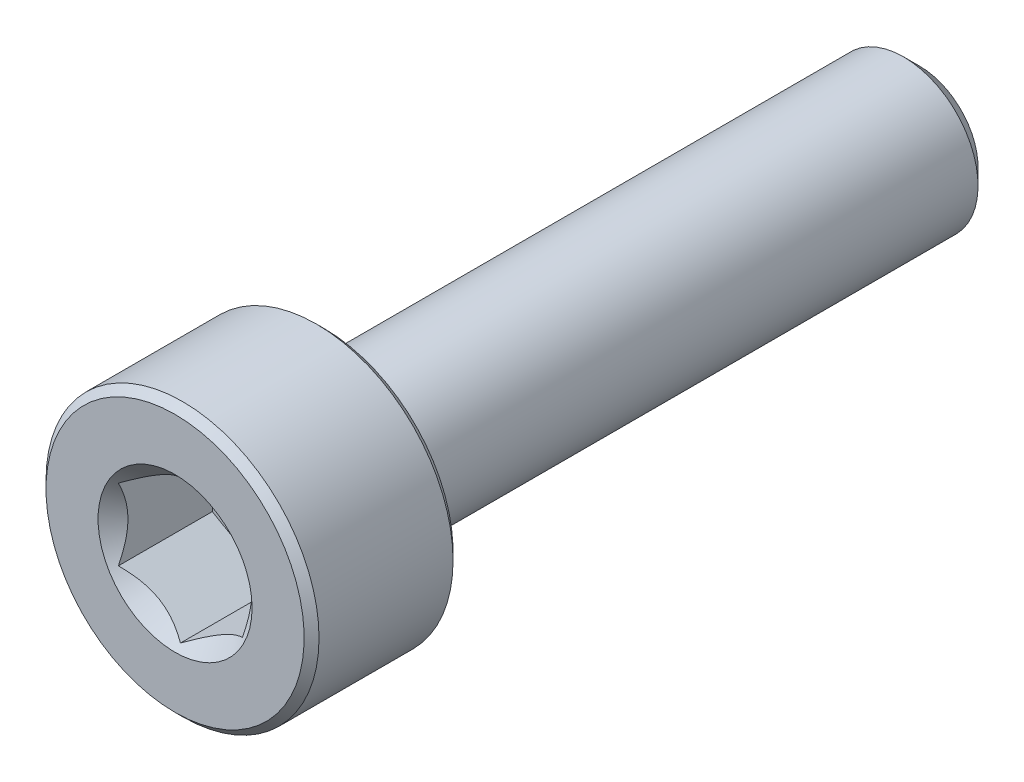
SolidWorks part; units mm, degrees
material "Alloy Steel"
ref_plane "Front Plane" through (0, 0, 0) normal (0, 0, 1) x (1, 0, 0)
ref_plane "Top Plane" through (0, 0, 0) normal (0, 1, 0) x (1, 0, 0)
ref_plane "Right Plane" through (0, 0, 0) normal (1, 0, 0) x (0, 0, -1)
sketch "Sketch1" plane through (0, 0, 0) normal (1, 0, 0) x (0, 0, -1)
  line L0 (-7.5, 0) -> (7.5, 0) construction
  line L1 (7.5, 0) -> (7.5, 1.1752) construction
  line L2 (7.5, 1.1752) -> (7.1752, 1.5) construction
  line L3 (7.1752, 1.5) -> (7.125, 1.5) construction
  line L4 (7.125, 1.5) -> (-4.5, 1.5) construction
  line L5 (-4.5, 1.5) -> (-4.5, 2.75) construction
  line L6 (-4.5, 2.75) -> (-7.5, 2.75) construction
  line L7 (-7.5, 2.75) -> (-7.5, 0) construction
  line L8 (7.5, 1.1752) -> (7.5, 1.5) construction
  line L9 (7.4687, 1.5541) -> (7.7187, 1.1211) construction
  line L10 (7.7187, 1.1211) -> (7.9687, 1.5541) construction
  line L11 (7.9687, 1.5541) -> (7.4687, 1.5541) construction
  line L12 (7.7187, 1.5541) -> (7.7188, 1.5) construction
  line L13 (7.7187, 1.1211) -> (7.7187, 1.1752) construction
  line L14 (7.6875, 1.1752) -> (7.75, 1.1752) construction
  line L15 (7.5, 1.5) -> (7.9375, 1.5) construction
  line L16 (7.4844, 1.5271) -> (7.9531, 1.5271) construction
  line L17 (7.5, 0) -> (7.5, -1.5) construction
  line L18 (-4.65, 2.75) -> (-4.5, 2.6) construction
  line L19 (-7.35, 2.75) -> (-7.5, 2.6) construction
  line L20 (-4.5, 1.5) -> (-4.5, 0) construction
  line L21 (-4.5, 0.75) -> (-0.5, 0.75) construction
  line L22 (-0.5, 0.75) -> (3.5, 0.75) construction
  line L23 (3.5, 0.75) -> (7.5, 0.75) construction
  line L24 (-0.5, 0.75) -> (-0.5, 1.5) construction
  line L25 (-0.5, 1.5) -> (-0.5, 2.75) construction
  line L26 (3.5, 0.75) -> (3.5, 2.75) construction
  point P0 (-7.5, 1.25)
  point P3 (6.25, 1.5)
  point P4 (0, 0)
  point P18 (3.5, 1.5)
  point P22 (7.7187, 1.1752)
  point P24 (7.125, 1.5)
  point P25 (7.7188, 1.5)
  point P28 (7.7187, 1.5271)
  point P29 (6.25, -1.5)
  point P30 (-0.5, 1.5)
  point P31 (-6, 2.75)
  point P37 (-5.025, 2.75)
  point P38 (-7.275, 2.75)
  point P45 (-0.5, 0.75)
  point P46 (3.5, 0.75)
  dimension "D2" = 0.0625
  dimension "D7" = 0.15
  dimension "D8" = 0.15
  dimension "D9" = 0.15
  dimension "D10" = 0.075
  dimension "D11" = 0.375
  dimension "Drive Size" = 2.5
  dimension "Head Diameter" = 5.5
  dimension "Head Height" = 3
  dimension "Thread Pitch" = 0.5
  dimension "Thread Dia" = 3
  dimension "Length" = 12
  dimension "D12" = 0.375
  dimension "D4" = 1.25
  dimension "D3" = 45
sketch "Sketch2" plane through (0, 0, 0) normal (1, 0, 0) x (0, 0, -1)
  line L0 (-7.5, 0) -> (-7.5, 2.6)
  line L1 (-7.35, 2.75) -> (-4.65, 2.75)
  line L2 (-4.5, 2.6) -> (-4.5, 1.65)
  line L4 (7.1752, 1.5) -> (7.5, 1.1752)
  line L5 (7.5, 1.1752) -> (7.5, 0)
  line L6 (-4.5, 2.75) -> (-7.5, 2.75) construction
  line L7 (7.5, 0) -> (-7.5, 0)
  line L8 (-7.35, 2.75) -> (-7.5, 2.6) construction
  line L10 (-7.35, 2.75) -> (-7.5, 2.6)
  line L14 (-4.65, 2.75) -> (-4.5, 2.6) construction
  line L16 (-4.65, 2.75) -> (-4.5, 2.6)
  line L17 (-4.5, 1.5) -> (-4.5, 2.75) construction
  line L19 (-4.35, 1.5) -> (7.1752, 1.5)
  line L20 (7.125, 1.5) -> (-4.5, 1.5) construction
  arc A1 (-4.5, 1.65) -> (-4.35, 1.5) centre (-4.35, 1.65) ccw
  dimension "D3" = 0.15
revolve "Revolve1" add sketch "Sketch2" angle 360 about L7
sketch "Sketch3" plane through (0, 0, 7.5) normal (0, 0, 1) x (1, 0, 0)
  line L1 (1.25, -0.7217) -> (1.25, 0.7217)
  line L2 (1.25, 0.7217) -> (0, 1.4434)
  line L3 (0, 1.4434) -> (-1.25, 0.7217)
  line L4 (-1.25, 0.7217) -> (-1.25, -0.7217)
  line L5 (-1.25, -0.7217) -> (0, -1.4434)
  line L6 (0, -1.4434) -> (1.25, -0.7217)
  circle A0 centre (0, 0) radius 1.25 construction
  circle A1 centre (0, 0) radius 2.75 construction
  circle A2 centre (0, 0) radius 2.75 construction
  circle A3 centre (0, 0) radius 1.4434 construction
  point P13 (0, 0)
  dimension "D1" = 2.8868
extrude "Cut-Extrude1" cut sketch "Sketch3" against normal offset from surface (2 mm away) 1 up to face at (0, 2.6, 4.5)
sketch "Sketch4" plane through (0, 0, 7.5) normal (0, 0, 1) x (1, 0, 0)
  circle A0 centre (0, 0) radius 1.5516
  dimension "D1" = 3.1033
extrude "Cut-Extrude2" cut sketch "Sketch4" against normal up to vertex (1.5 mm away) draft 45 up to point (0, 2.75, 6)
sketch "Sketch11" plane through (0, 0, 0) normal (1, 0, 0) x (0, 0, -1)
  line L0 (-7.5, 0) -> (7.5, 0) construction
  line L1 (-7.5, 0) -> (7.5, 0) construction
  line L2 (-2.25, 0) -> (-2.25, 1.5) construction
  line L3 (7.125, 1.5) -> (-4.5, 1.5) construction
  line L4 (5.25, 0) -> (5.25, 1.5) construction
  line L6 (7.5, 1.1752) -> (7.5, 1.5) construction
  point P2 (-2.25, 0)
  point P3 (5.25, 0)
  dimension "D1" = 2.25
  dimension "D2" = 2.25
sketch "Sketch6" [suppressed] plane through (0, 0, -7.5) normal (0, 0, -1) x (-1, 0, 0)
  circle A0 centre (0, 0) radius 1.5
curve "Helix/Spiral1" [suppressed] pitch 0.5 height 12.5 turns 25
sketch "Sketch10" [suppressed] plane through (0, 0, 0) normal (1, 0, 0) x (0, 0, -1)
  line L0 (-4.35, -2.75) -> (-4.35, 2.75)
  line L5 (-7.5, 0) -> (7.5, 0) construction
  line L6 (-4.35, 1.5) -> (-4.35, -1.5) construction
  point P3 (-4.35, 0)
split "Split1" [suppressed] bodies to split 106
sketch "Sketch7" [suppressed] plane through (0, 0, 0) normal (1, 0, 0) x (0, 0, -1)
  line L0 (7.4844, 1.5271) -> (7.9531, 1.5271)
  line L1 (7.9531, 1.5271) -> (7.75, 1.1752)
  line L2 (7.75, 1.1752) -> (7.6875, 1.1752)
  line L3 (7.6875, 1.1752) -> (7.4844, 1.5271)
sweep "Cut-Sweep1" [suppressed] cut profiles "Sketch7" path "Helix/Spiral1"
sketch "Sketch8" [suppressed] plane through (0, 0, 0) normal (1, 0, 0) x (0, 0, -1)
  line L0 (-4.5, 0) -> (-4.5, 1.5)
  line L1 (-4.35, -1.5) -> (-4.35, 1.5) construction
  line L2 (-4.5, 1.5) -> (-4.35, 1.5)
  line L4 (-4.35, 1.5) -> (-3.484, 0)
  line L5 (-3.484, 0) -> (-4.5, 0)
  line L6 (7.125, 1.5) -> (-4.5, 1.5) construction
  line L7 (-7.5, 0) -> (7.5, 0) construction
  dimension "D1" = 60
revolve "Revolve2" [suppressed] add sketch "Sketch8" angle 360 about L5
equation "\"D2@Sketch1\" = \"Thread Pitch@Sketch1\" / 8"
equation "\"D4@Helix/Spiral1\" = \"Thread Pitch@Sketch1\""
equation "\"D7@Sketch1\" = \"Head Height@Sketch1\" * .05"
equation "\"D8@Sketch1\"=\"D7@Sketch1\""
equation "\"D9@Sketch1\"=\"D7@Sketch1\""
equation "\"D10@Sketch1\"=\"D7@Sketch1\"/2"
equation "\"D11@Sketch1\"=\"D10@Sketch1\"*5"
equation "\"D4@Sketch1\"=\"Thread Pitch@Sketch1\"*2.5"
equation "\"D12@Sketch1\"=\"Thread Pitch@Sketch1\"*.75"
equation "\"D3@Helix/Spiral1\"=\"Length@Sketch1\"+\"Thread Pitch@Sketch1\""
equation "\"D3@Sketch2\"=\"Thread Dia@Sketch1\"*0.05"
equation "\"D1@Sketch11\"=\"Length@Sketch1\"*0.1875"
equation "\"D2@Sketch11\"=\"D1@Sketch11\""
equation "\"D1@Sketch4\"=\"D1@Sketch3\"*1.075"
